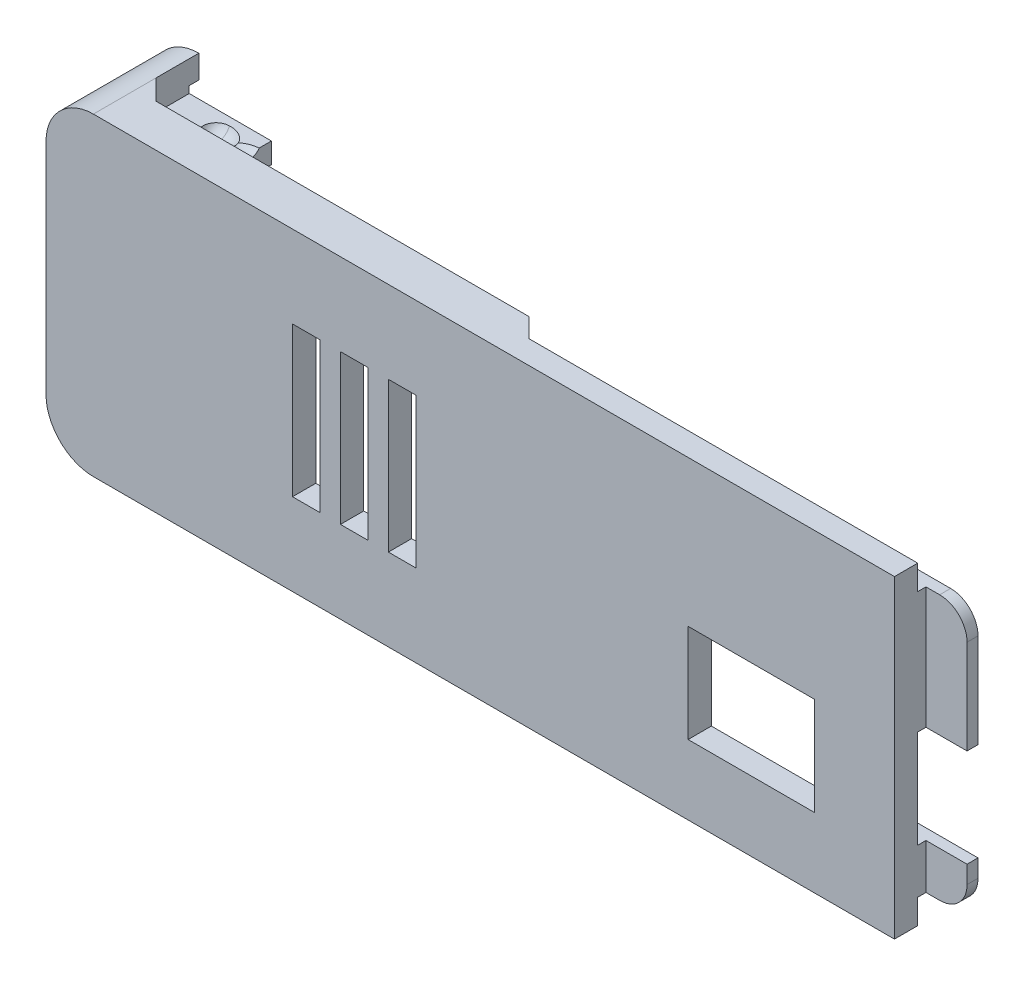
SolidWorks part; units mm, degrees
ref_plane "Front Plane" through (0, 0, 0) normal (0, 0, 1) x (1, 0, 0)
ref_plane "Top Plane" through (0, 0, 0) normal (0, 1, 0) x (1, 0, 0)
ref_plane "Right Plane" through (0, 0, 0) normal (1, 0, 0) x (0, 0, -1)
sketch "Sketch1" plane through (0, 0, 0) normal (0, 0, 1) x (1, 0, 0)
  line L1 (1.5692, 30.8817) -> (1.5692, 46.8537)
  line L2 (5.0292, 27.4038) -> (5.0292, 29.1038)
  line L3 (3.2692, 30.8817) -> (3.2692, 46.8537)
  line L4 (5.0292, 48.6316) -> (5.0292, 50.3317)
  arc A1 (5.038, 48.6317) -> (3.2692, 46.8537) centre (5.0472, 46.8537) ccw construction
  arc A2 (5.0292, 50.3317) -> (1.5692, 46.8537) centre (5.0472, 46.8537) ccw
  arc A3 (1.5692, 30.8817) -> (5.0292, 27.4038) centre (5.0472, 30.8817) ccw
  arc A4 (5.0292, 48.6316) -> (3.2692, 46.8537) centre (5.0472, 46.8537) ccw
  arc A5 (3.2692, 30.8817) -> (5.0292, 29.1038) centre (5.0472, 30.8817) ccw
  arc A6 (3.2692, 30.8817) -> (5.038, 29.1037) centre (5.0472, 30.8817) ccw construction
  dimension "D2" = 1.7
  dimension "D1" = 3.46
extrude "Boss-Extrude2" add sketch "Sketch1" along normal blind 7.7
sketch "Sketch3" plane through (5.0292, 0, 0) normal (1, 0, 0) x (0, 0, -1)
  line L0 (-7.7, 48.6316) -> (-7.7, 50.3317) construction
  line L1 (-7.7, 48.6316) -> (-6.1, 48.6316) construction
  line L2 (-7.7, 48.6316) -> (-7.7, 50.3317)
  line L3 (-7.7, 50.3317) -> (-6.1, 50.3317)
  line L4 (-6.1, 48.6316) -> (-6.1, 50.3317)
  line L5 (-7.7, 48.6316) -> (0, 48.6316) construction
  line L6 (-7.7, 50.3317) -> (0, 50.3317) construction
  line L7 (-7.7, 48.6316) -> (-7.7, 48.5316)
  line L8 (-7.7, 48.5316) -> (-6.1, 48.5316)
  line L9 (-6.1, 48.5316) -> (-6.1, 48.6316)
  dimension "D1" = 1.6
  dimension "D2" = 0.1
extrude "Boss-Extrude3" add sketch "Sketch3" along normal offset from surface (58.494 mm away) 0.2
sketch "Sketch4" plane through (0, 50.3317, 0) normal (0, 1, 0) x (1, 0, 0)
  line L1 (35.2317, -6.1) -> (5.0292, -6.1)
  line L18 (35.2024, -6.0707) -> (35.2317, -6.1)
  line L19 (63.5232, -6.1) -> (5.0292, -6.1) construction
  line L20 (5.0292, -6.1) -> (5.0292, -3.1234)
  line L21 (35.2024, -6.0707) -> (33.7317, -4.6)
  line L22 (33.7317, -4.6) -> (6.5057, -4.6)
  line L23 (6.5057, -4.6) -> (5.0292, -3.1234)
  line L24 (5.0292, -6.1) -> (5.0292, 0) construction
  dimension "D1" = 45
  dimension "D2" = 1.5
  dimension "D3" = 45
extrude "Boss-Extrude4" add sketch "Sketch4" against normal up to surface (1.8 mm away) up to face at (34.2762, 48.5316, 6.9)
sketch "Sketch7" plane through (0, 48.5316, 0) normal (0, -1, 0) x (1, 0, 0)
  line L0 (5.0292, 7.7) -> (5.0292, 3.1234) construction
  line L1 (5.0292, 7.7) -> (11.0292, 7.7)
  line L2 (5.0292, 7.7) -> (5.0292, 0.7)
  line L3 (5.0292, 0.7) -> (11.0292, 0.7)
  line L4 (11.0292, 7.7) -> (11.0292, 0.7)
  dimension "D1" = 6
  dimension "D2" = 7
extrude "Boss-Extrude5" add sketch "Sketch7" along normal blind 1.9
sketch "Sketch8" plane through (0, 48.5316, 0) normal (0, 1, 0) x (1, 0, 0)
  line L1 (7.4932, -2.25) -> (9.5932, -2.25)
  line L2 (11.0292, -0.7) -> (11.0292, -4.6) construction
  line L3 (9.5932, -2.25) -> (11.0292, -2.25)
  line L4 (11.0292, -2.25) -> (11.0292, -3.0132)
  line L6 (9.9522, -2.25) -> (9.9522, -2.7) construction
  arc A0 (7.4932, -2.25) -> (8.5432, -3.3) centre (8.5432, -2.25) ccw
  spline S0 degree 2 poles (11.0292, -3.0132) (10.4556, -2.9792) (9.9522, -2.7) knots 0 0 0 1 1 1
  spline S1 degree 2 poles (8.5432, -3.3) (9.3663, -3.3395) (9.9522, -2.7) knots 0 0 0 1 1 1
  point P12 (0, 0)
  point P13 (9.1031, -3.241)
  point P14 (0, 0)
  dimension "D1" = 2.1
  dimension "D2" = 2.1
  dimension "D3" = 0.45
  dimension "D4" = 1.436
  dimension "D5" = 1.077
revolve "Cut-Revolve1" cut sketch "Sketch8" angle 360 about L1
sketch "Sketch9" plane through (11.0292, 0, 0) normal (1, 0, 0) x (0, 0, -1)
  line L0 (-3.0132, 48.5316) -> (-4.6, 48.5316) construction
  line L1 (-0.7, 48.5316) -> (-5.7, 48.5316)
  line L2 (-0.7, 48.5316) -> (-0.7, 48.1316)
  line L3 (-0.7, 48.1316) -> (-5.7, 48.1316)
  line L4 (-5.7, 48.5316) -> (-5.7, 48.1316)
  line L5 (-0.7, 46.6316) -> (-0.7, 48.5316) construction
  dimension "D1" = 0.4
  dimension "D2" = 5
extrude "Cut-Extrude1" cut sketch "Sketch9" against normal up to surface (6 mm away) up to face at (5.0292, 47.9316, 3.8411)
sketch "Sketch10" plane through (0, 48.5316, 0) normal (0, -1, 0) x (-1, 0, 0)
  line L0 (-63.5232, -7.7) -> (-11.0292, -7.7) construction
  line L1 (-11.8895, -7.7) -> (-63.5232, -7.7)
  line L2 (-11.8895, -7.7) -> (-11.8895, -4.6)
  line L3 (-11.8895, -4.6) -> (-63.5232, -4.6)
  line L4 (-63.5232, -7.7) -> (-63.5232, -4.6)
  line L5 (-6.5057, -4.6) -> (-33.7317, -4.6) construction
extrude "Boss-Extrude6" add sketch "Sketch10" along normal blind 1
ref_plane "Plane4" through (0, 27.4038, 0) normal (0, 1, 0) x (0, 0, -1)
ref_plane "Plane5" through (0, 38.8677, 0) normal (0, 1, 0) x (1, 0, 0)
mirror "Mirror1" about plane through (0, 38.8677, 0) normal (0, 1, 0) of "Boss-Extrude4", "Cut-Revolve1", "Boss-Extrude5", "Boss-Extrude2", "Boss-Extrude6", "Boss-Extrude3"
sketch "Sketch12" plane through (0, 0, 7.7) normal (0, 0, 1) x (1, 0, 0)
  line L0 (63.5232, 50.3317) -> (5.0292, 50.3317) construction
  line L1 (63.5232, 27.4038) -> (5.0292, 27.4038) construction
  line L2 (1.5692, 46.8537) -> (1.5692, 30.8817) construction
  line L3 (63.5232, 50.3317) -> (5.0292, 50.3317)
  line L4 (63.5232, 27.4038) -> (5.0292, 27.4038)
  line L5 (1.5692, 46.8537) -> (1.5692, 30.8817)
  line L6 (63.5232, 50.3317) -> (63.5232, 27.4038)
  arc A0 (1.5692, 30.8817) -> (5.0292, 27.4038) centre (5.0472, 30.8817) ccw construction
  arc A1 (5.0292, 50.3317) -> (1.5692, 46.8537) centre (5.0472, 46.8537) ccw construction
  arc A2 (1.5692, 30.8817) -> (5.0292, 27.4038) centre (5.0472, 30.8817) ccw
  arc A3 (5.0292, 50.3317) -> (1.5692, 46.8537) centre (5.0472, 46.8537) ccw
extrude "Boss-Extrude7" add sketch "Sketch12" against normal blind 1.7
sketch "Sketch14" plane through (63.5232, 0, 0) normal (1, 0, 0) x (0, 0, -1)
  line L0 (-4.6, 48.5316) -> (-6, 48.5316) construction
  line L1 (-4.6, 29.2038) -> (-6, 29.2038)
  line L2 (-4.6, 29.2038) -> (-4.6, 48.5316)
  line L3 (-4.6, 48.5316) -> (-6, 48.5316)
  line L4 (-6, 29.2038) -> (-6, 48.5316)
extrude "Boss-Extrude12" add sketch "Sketch14" along normal blind 3 and the other way blind 1.7
fillet "Fillet1" radius 2 2 edges at (66.5232, 48.5316, 5.3) (66.5232, 29.2038, 5.3)
sketch "Sketch15" plane through (0, 0, 6) normal (0, 0, 1) x (1, 0, 0)
  line L0 (63.5232, 29.2038) -> (64.5232, 29.2038) construction
  line L1 (66.5232, 46.5316) -> (66.5232, 31.2038) construction
  line L2 (63.5232, 29.2038) -> (63.5232, 48.5316) construction
  line L3 (63.5232, 48.5316) -> (64.5232, 48.5316) construction
  line L4 (63.5232, 29.2038) -> (64.5232, 29.2038)
  line L5 (66.5232, 46.5316) -> (66.5232, 31.2038)
  line L6 (63.5232, 29.2038) -> (63.5232, 48.5316)
  line L7 (63.5232, 48.5316) -> (64.5232, 48.5316)
  arc A0 (64.5232, 29.2038) -> (66.5232, 31.2038) centre (64.5232, 31.2038) ccw construction
  arc A1 (66.5232, 46.5316) -> (64.5232, 48.5316) centre (64.5232, 46.5316) ccw construction
  arc A2 (64.5232, 29.2038) -> (66.5232, 31.2038) centre (64.5232, 31.2038) ccw
  arc A3 (66.5232, 46.5316) -> (64.5232, 48.5316) centre (64.5232, 46.5316) ccw
extrude "Cut-Extrude2" cut sketch "Sketch15" against normal blind 0.6
sketch "Sketch16" plane through (1.5692, 0, 0) normal (-1, 0, 0) x (0, 0, 1)
  line L0 (7.7, 38.8677) -> (0, 38.8677) construction
  line L1 (7.7, 46.8537) -> (7.7, 30.8817) construction
  line L2 (0, 46.8537) -> (0, 30.8817) construction
  line L3 (3.125, 35.6927) -> (3.125, 42.0427) construction
  line L4 (1.3, 35.6927) -> (1.3, 42.0427)
  line L5 (4.95, 35.6927) -> (4.95, 42.0427)
  arc A0 (1.3, 35.6927) -> (4.95, 35.6927) centre (3.125, 35.6927) ccw
  arc A1 (4.95, 42.0427) -> (1.3, 42.0427) centre (3.125, 42.0427) ccw
  point P8 (3.125, 38.8677)
  dimension "D1" = 3.65
  dimension "D2" = 6.35
  dimension "D3" = 2.75
extrude "Cut-Extrude3" cut sketch "Sketch16" against normal up to surface (1.7 mm away) up to face at (3.2692, 38.8677, 3)
sketch "Sketch18" plane through (0, 0, 6) normal (0, 0, -1) x (-1, 0, 0)
  line L1 (-5.0292, 46.6316) -> (-3.0292, 46.6316)
  line L2 (-5.0292, 46.6316) -> (-5.0292, 48.7316)
  line L3 (-5.0292, 48.7316) -> (-3.0292, 48.7316)
  line L4 (-3.0292, 46.6316) -> (-3.0292, 48.7316)
  line L5 (-5.0292, 31.1038) -> (-3.0292, 31.1038)
  line L6 (-5.0292, 31.1038) -> (-5.0292, 29.0038)
  line L7 (-5.0292, 29.0038) -> (-3.0292, 29.0038)
  line L8 (-3.0292, 31.1038) -> (-3.0292, 29.0038)
  dimension "D1" = 2
  dimension "D2" = 2.1
  dimension "D3" = 2
  dimension "D4" = 2.1
extrude "Boss-Extrude13" add sketch "Sketch18" along normal up to surface (5.3 mm away) up to face at (8.0292, 47.3816, 0.7)
sketch "Sketch19" plane through (0, 0, 7.7) normal (0, 0, 1) x (1, 0, 0)
  line L1 (48.4548, 32.4935) -> (57.6984, 32.4935)
  line L2 (48.4548, 32.4935) -> (48.4548, 39.6518)
  line L3 (48.4548, 39.6518) -> (57.6984, 39.6518)
  line L4 (57.6984, 32.4935) -> (57.6984, 39.6518)
extrude "Cut-Extrude4" cut sketch "Sketch19" against normal blind 1.7
sketch "Sketch20" plane through (0, 0, 4.6) normal (0, 0, -1) x (-1, 0, 0)
  line L0 (-57.6984, 39.6518) -> (-48.4548, 39.6518) construction
  line L1 (-48.4548, 32.4935) -> (-57.6984, 32.4935) construction
  line L2 (-57.6984, 39.6518) -> (-48.4548, 39.6518) construction
  line L3 (-48.4548, 32.4935) -> (-57.6984, 32.4935) construction
  line L4 (-61.8232, 30.2038) -> (-61.8232, 47.5316) construction
  line L5 (-61.8232, 39.6518) -> (-66.5232, 39.6518)
  line L6 (-61.8232, 39.6518) -> (-61.8232, 32.4935)
  line L7 (-61.8232, 32.4935) -> (-66.5232, 32.4935)
  line L8 (-66.5232, 39.6518) -> (-66.5232, 32.4935)
  line L9 (-66.5232, 31.2038) -> (-66.5232, 46.5316) construction
extrude "Cut-Extrude5" cut sketch "Sketch20" against normal up to surface (1.4 mm away) up to face at (53.0766, 36.0726, 6)
sketch "Sketch21" plane through (0, 0, 7.7) normal (0, 0, 1) x (1, 0, 0)
  line L0 (1.5692, 46.8537) -> (1.5692, 30.8817) construction
  line L1 (19.5692, 33.4038) -> (21.5692, 33.4038)
  line L2 (19.5692, 33.4038) -> (19.5692, 44.3317)
  line L3 (19.5692, 44.3317) -> (21.5692, 44.3317)
  line L4 (21.5692, 33.4038) -> (21.5692, 44.3317)
  line L5 (63.5232, 27.4038) -> (5.0292, 27.4038) construction
  line L6 (63.5232, 50.3317) -> (5.0292, 50.3317) construction
  line L8 (23.0692, 44.3317) -> (25.0692, 44.3317)
  line L9 (23.0692, 44.3317) -> (23.0692, 33.4038)
  line L10 (23.0692, 33.4038) -> (25.0692, 33.4038)
  line L11 (25.0692, 44.3317) -> (25.0692, 33.4038)
  line L12 (26.5692, 44.3317) -> (28.5692, 44.3317)
  line L13 (26.5692, 44.3317) -> (26.5692, 33.4038)
  line L14 (26.5692, 33.4038) -> (28.5692, 33.4038)
  line L15 (28.5692, 44.3317) -> (28.5692, 33.4038)
  point P8 (20.5692, 44.3317)
  dimension "D1" = 18
  dimension "D2" = 6
  dimension "D3" = 6
  dimension "D4" = 2
  dimension "D5" = 1.5
  dimension "D6" = 2
  dimension "D7" = 2
  dimension "D8" = 1.5
extrude "Cut-Extrude6" cut sketch "Sketch21" against normal through all
equation "\"D2@Sketch16\"=10-\"D1@Sketch16\""
equation "\"D3@Sketch21\"=\"D2@Sketch21\""
equation "\"D6@Sketch21\"=\"D4@Sketch21\""
equation "\"D7@Sketch21\"=\"D4@Sketch21\""
equation "\"D8@Sketch21\"=\"D5@Sketch21\""
equation "\"D5@Sketch8\"=0.75*\"D4@Sketch8\""
